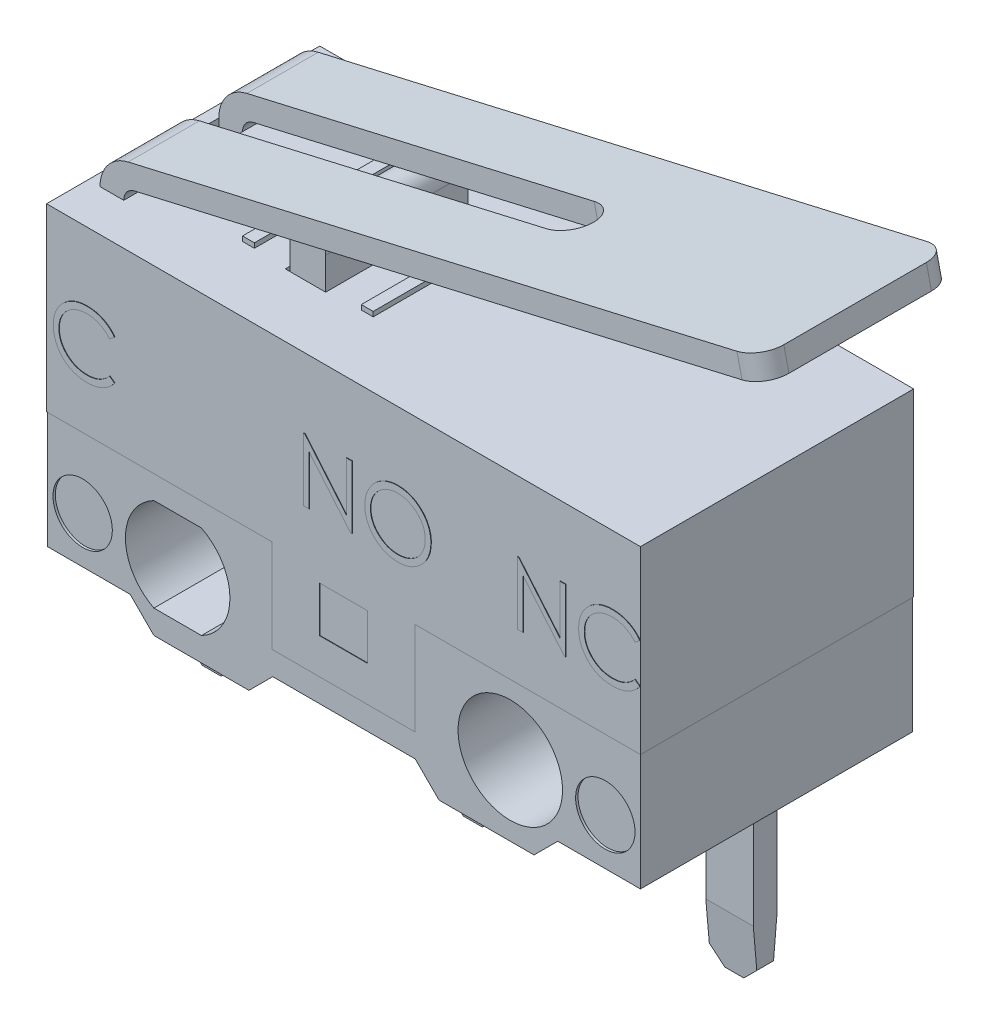
SolidWorks part; units mm, degrees
ref_plane "Plan de face" through (0, 0, 0) normal (0, 0, 1) x (1, 0, 0)
ref_plane "Plan de dessus" through (0, 0, 0) normal (0, 1, 0) x (1, 0, 0)
ref_plane "Plan de droite" through (0, 0, 0) normal (1, 0, 0) x (0, 0, -1)
sketch "Esquisse1" plane through (0, 0, 0) normal (0, 0, 1) x (1, 0, 0)
  line L1 (-6.5, 3.375) -> (6.5, 3.375)
  line L2 (-6.5, 3.375) -> (-6.5, -3.375)
  line L3 (-6.5, -3.375) -> (6.5, -3.375)
  line L4 (6.5, 3.375) -> (6.5, -3.375)
  line L5 (-6.5, 3.375) -> (6.5, -3.375) construction
  line L6 (-6.5, -3.375) -> (6.5, 3.375) construction
  point P0 (0, 0)
  dimension "D1" = 6.75
  dimension "D2" = 13
extrude "Boss.-Extru.1" add sketch "Esquisse1" along normal blind 5.75
ref_plane "Plan1" through (0, 0, 2.875) normal (0, 0, 1) x (1, 0, 0)
sketch "Esquisse6" plane through (0, 0, 5.75) normal (0, 0, 1) x (1, 0, 0)
  line L0 (-6.5, -2.875) -> (-4.5, -2.875)
  line L1 (-6.5, 3.375) -> (-6.5, -3.375) construction
  line L2 (-4.5, -2.875) -> (-4, -3.375)
  line L3 (-6.5, -3.375) -> (6.5, -3.375) construction
  line L4 (-4, -3.375) -> (-2, -3.375)
  line L5 (-2, -3.375) -> (-1.5, -2.875)
  line L6 (-1.5, -2.875) -> (1.5, -2.875)
  line L7 (1.5, -2.875) -> (2, -3.375)
  line L8 (2, -3.375) -> (4, -3.375)
  line L9 (4, -3.375) -> (4.5, -2.875)
  line L10 (4.5, -2.875) -> (6.5, -2.875)
  line L11 (6.5, -3.375) -> (6.5, 3.375) construction
  line L12 (6.5, -2.875) -> (6.5, -4.2145)
  line L13 (6.5, -4.2145) -> (-6.5, -4.2145)
  line L14 (-6.5, -4.2145) -> (-6.5, -2.875)
  dimension "D1" = 0.5
  dimension "D2" = 135
  dimension "D3" = 135
  dimension "D4" = 135
  dimension "D5" = 2
  dimension "D6" = 2
  dimension "D7" = 2
  dimension "D8" = 2
extrude "Enlèv. mat.-Extru.1" cut sketch "Esquisse6" against normal up to surface (5.75 mm away) up to face at (0, 0, 0)
sketch "Esquisse4" plane through (0, 0, 2.875) normal (0, 0, 1) x (1, 0, 0)
  line L0 (-6, -2.875) -> (-6, -6.125)
  line L9 (-5, -6.125) -> (-5, -2.875)
  line L10 (-5, -2.875) -> (-6, -2.875)
  line L11 (-5.5, -2.875) -> (-5.5, -7.9439) construction
  line L15 (-6, -6.125) -> (-5, -6.125)
  line L16 (-4.5, -2.875) -> (-6.5, -2.875) construction
  line L17 (-6.5, 3.375) -> (-6.5, -2.875) construction
  dimension "D1" = 1
  dimension "D2" = 1
  dimension "D4" = 3.25
extrude "Boss.-Extru.2" add sketch "Esquisse4" along normal blind 0.25 and the other way blind 0.25
chamfer "Chanfrein1" distance 0.3 angle 45 2 edges at (-5, -6.125, 2.875) (-6, -6.125, 2.875)
chamfer "Chanfrein2" distance 0.1 angle 85 2 edges at (-5.5, -6.125, 2.625) (-5.5, -6.125, 3.125)
pattern_linear "Répétition linéaire1" count 3 spacing 5.5 along (1, 0, 0) of "Boss.-Extru.2", "Chanfrein1", "Chanfrein2"
sketch "Esquisse7" plane through (0, 0, 5.75) normal (0, 0, 1) x (1, 0, 0)
  line L0 (-4, -2.875) -> (-3, -2.875)
  line L1 (-4, -0.9154) -> (-3, -0.9154)
  line L2 (-3.5, -1.8952) -> (3.5, -1.8952) construction
  line L3 (-4, -3.375) -> (-2, -3.375) construction
  line L4 (-6.5, 3.375) -> (-6.5, -2.875) construction
  line L5 (6.5, -2.875) -> (6.5, 3.375) construction
  arc A0 (-4, -0.9154) -> (-4, -2.875) centre (-3.5, -1.8952) ccw
  arc A1 (-3, -0.9154) -> (-3, -2.875) centre (-3.5, -1.8952) cw
  circle A2 centre (3.5, -1.8952) radius 1.1
  dimension "D1" = 1.1
  dimension "D3" = 1.1
  dimension "D4" = 2.2
  dimension "D2" = 1
  dimension "D5" = 0.5
  dimension "D6" = 3
  dimension "D7" = 3
extrude "Enlèv. mat.-Extru.2" cut sketch "Esquisse7" against normal up to surface (5.75 mm away) up to face at (0, -2, 0)
sketch "Esquisse8" plane through (0, 0, 5.75) normal (0, 0, 1) x (1, 0, 0)
  line L0 (-6.5, -0.4154) -> (-1.5, -0.4154)
  line L1 (-6.5, 3.375) -> (-6.5, -2.875) construction
  line L2 (-1.5, -0.4154) -> (-1.5, -2.375)
  line L3 (-1.5, -2.375) -> (1.5, -2.375)
  line L4 (1.5, -2.375) -> (1.5, -0.4154)
  line L5 (1.5, -0.4154) -> (6.5, -0.4154)
  line L6 (6.5, -2.875) -> (6.5, 3.375) construction
  line L7 (6.5, -0.4154) -> (6.5, -4.9919)
  line L8 (6.5, -4.9919) -> (-6.5, -4.9919)
  line L9 (-6.5, -4.9919) -> (-6.5, -0.4154)
  line L10 (1.5, -2.875) -> (-1.5, -2.875) construction
  line L11 (-3, -0.9154) -> (-4, -0.9154) construction
  line L13 (-0.5, -0.6654) -> (0.5, -0.6654)
  line L14 (-0.5, -0.6654) -> (-0.5, -1.625)
  line L15 (-0.5, -1.625) -> (0.5, -1.625)
  line L16 (0.5, -0.6654) -> (0.5, -1.625)
  line L17 (-0.5, -0.6654) -> (0.5, -1.625) construction
  line L18 (-0.5, -1.625) -> (0.5, -0.6654) construction
  point P21 (0, -1.1452)
  dimension "D1" = 0.5
  dimension "D2" = 0.5
  dimension "D3" = 0.25
  dimension "D4" = 1
  dimension "D5" = 1
  dimension "D6" = 0.75
extrude "Enlèv. mat.-Extru.3" cut sketch "Esquisse8" against normal blind 0.01
sketch "Esquisse9" plane through (0, 0, 5.74) normal (0, 0, 1) x (1, 0, 0)
  line L0 (-5.5, -1.8952) -> (5.5, -1.8952) construction
  line L1 (6.5, -2.875) -> (6.5, -0.4154) construction
  line L2 (-6.5, -0.4154) -> (-6.5, -2.875) construction
  circle A0 centre (-5.5, -1.8952) radius 0.625
  circle A1 centre (5.5, -1.8952) radius 0.625
  point P4 (3.5, -1.8952)
  dimension "D1" = 1.25
  dimension "D2" = 1.25
  dimension "D3" = 1
  dimension "D4" = 1
extrude "Enlèv. mat.-Extru.4" cut sketch "Esquisse9" against normal blind 0.05
mirror "Symétrie1" about plane through (0, 0, 2.875) normal (0, 0, 1) of "Enlèv. mat.-Extru.4", "Enlèv. mat.-Extru.3"
sketch "Esquisse10" plane through (-6.5, 0, 0) normal (-1, 0, 0) x (0, 0, 1)
  line L1 (0.01, -2.875) -> (5.74, -2.875)
  line L2 (0.01, -2.875) -> (0.01, -0.4154)
  line L3 (0.01, -0.4154) -> (5.74, -0.4154)
  line L4 (5.74, -2.875) -> (5.74, -0.4154)
extrude "Enlèv. mat.-Extru.5" cut sketch "Esquisse10" against normal blind 0.01
sketch "Esquisse11" plane through (6.5, 0, 0) normal (1, 0, 0) x (0, 0, -1)
  line L1 (-5.74, -2.875) -> (-0.01, -2.875)
  line L2 (-5.74, -2.875) -> (-5.74, -0.4154)
  line L3 (-5.74, -0.4154) -> (-0.01, -0.4154)
  line L4 (-0.01, -2.875) -> (-0.01, -0.4154)
extrude "Enlèv. mat.-Extru.6" cut sketch "Esquisse11" against normal blind 0.01
sketch "Esquisse12" plane through (0, 0, 5.75) normal (0, 0, 1) x (1, 0, 0)
  line L0 (-6.2, 0.5846) -> (-4.55, 0.5846) construction
  line L4 (-1, 0.5846) -> (2.5, 0.5846) construction
  line L5 (3.5, 0.5846) -> (6.2, 0.5846) construction
  line L6 (-1.5, -0.4154) -> (-6.5, -0.4154) construction
  line L7 (-6.5, 3.375) -> (-6.5, -0.4154) construction
  line L8 (6.5, -0.4154) -> (6.5, 3.375) construction
  text T0 "C" font "Century Gothic" height in points 5
  text T1 "NO" font "Century Gothic" height in points 5
  text T2 "NC" font "Century Gothic" height in points 5
  dimension "D1" = 1
  dimension "D2" = 1.65
  dimension "D3" = 0.3
  dimension "D4" = 0.3
  dimension "D5" = 2.7
  dimension "D6" = 3.5
  dimension "D7" = 1
extrude "Boss.-Extru.3" add sketch "Esquisse12" along normal blind 0.01
sketch "Esquisse13" plane through (0, 0, 2.875) normal (0, 0, 1) x (1, 0, 0)
  line L0 (-1.75, 4) -> (-1.75, 3.375)
  line L1 (6.5, 3.375) -> (-6.5, 3.375) construction
  line L2 (-1.75, 3.375) -> (-2.5, 3.375)
  line L3 (-2.5, 3.375) -> (-2.5, 4)
  line L4 (-4.7467, 4.375) -> (-2.1308, 4.375) construction
  line L5 (-6.5, 3.375) -> (-6.5, -0.4154) construction
  line L6 (-3.5, 3.375) -> (-3.5, 3.475)
  line L7 (-3.5, 3.475) -> (-3.25, 3.475)
  line L8 (-3.25, 3.475) -> (-3.25, 3.375)
  line L9 (-3.25, 3.375) -> (-3.5, 3.375)
  line L10 (-1, 3.375) -> (-1, 3.475)
  line L11 (-1, 3.475) -> (-0.75, 3.475)
  line L12 (-0.75, 3.475) -> (-0.75, 3.375)
  line L13 (-0.75, 3.375) -> (-1, 3.375)
  arc A0 (-2.5, 4) -> (-1.75, 4) centre (-2.125, 4) cw
  dimension "D1" = 0.75
  dimension "D2" = 1
  dimension "D3" = 4
  dimension "D4" = 0.1
  dimension "D5" = 0.75
  dimension "D6" = 0.75
  dimension "D7" = 0.25
  dimension "D8" = 0.25
extrude "Boss.-Extru.4" add sketch "Esquisse13" along normal blind 1.5 and the other way blind 1.5
sketch "Esquisse14" plane through (0, 3.375, 0) normal (0, 1, 0) x (1, 0, 0)
  line L1 (-2.5, -1.375) -> (-1.75, -1.375)
  line L2 (-2.5, -1.375) -> (-2.5, -4.375)
  line L3 (-2.5, -4.375) -> (-1.75, -4.375)
  line L4 (-1.75, -1.375) -> (-1.75, -4.375)
  line L8 (-6.5, -5.75) -> (-6.5, 0) construction
  line L9 (-6, -0.875) -> (-5.5, -0.875)
  line L10 (-6, -0.875) -> (-6, -4.875)
  line L11 (-6, -4.875) -> (-5.5, -4.875)
  line L12 (-2.55, -1.325) -> (-2.55, -4.425)
  line L13 (-2.55, -4.425) -> (-1.7, -4.425)
  line L14 (-1.7, -4.425) -> (-1.7, -1.325)
  line L15 (-1.7, -1.325) -> (-2.55, -1.325)
  line L16 (-2.55, -1.325) -> (-2.55, -4.425)
  line L17 (-2.55, -4.425) -> (-1.7, -4.425)
  line L18 (-1.7, -4.425) -> (-1.7, -1.325)
  line L19 (-1.7, -1.325) -> (-2.55, -1.325)
  line L20 (-5.5, -0.875) -> (-5.5, -4.875)
  line L21 (-6, -2.875) -> (-3.9155, -2.875) construction
  line L22 (-3.7125, -2.875) -> (3.7125, -2.875) construction
  dimension "D2" = 0.5
  dimension "D3" = 0.5
  dimension "D4" = 4
  dimension "D1" = 0.05
extrude "Enlèv. mat.-Extru.7" cut sketch "Esquisse14" against normal blind 2
sketch "Esquisse16" plane through (0, 0, 0.875) normal (0, 0, 1) x (1, 0, 0)
  line L0 (-6, 2.375) -> (-5.5, 2.375)
  line L1 (-5.5, 2.375) -> (-5.5, 3.375)
  line L2 (-5.2748, 3.6581) -> (8, 6.7211)
  line L3 (8, 6.7211) -> (7.8921, 7.1888)
  line L4 (7.8921, 7.1888) -> (-5.4072, 4.1201)
  line L5 (-6, 3.375) -> (-6, 2.375)
  line L6 (-6.5, 3.375) -> (-6.5, -0.4154) construction
  line L7 (6.5, 3.375) -> (-6.5, 3.375) construction
  line L8 (8, 6.7211) -> (8, 3.9001) construction
  line L9 (6.5, -0.4154) -> (6.5, 3.375) construction
  line L10 (6.5, 2.5145) -> (6.5, 9.8405) construction
  arc A0 (-5.5, 3.375) -> (-5.2748, 3.6581) centre (-5.2095, 3.375) cw
  arc A2 (-1.75, 4) -> (-2.5, 4) centre (-2.125, 4) ccw construction
  arc A3 (-6, 3.375) -> (-5.4072, 4.1201) centre (-5.2353, 3.375) cw
  point P8 (6.5, 6.375)
  dimension "D1" = 0.5
  dimension "D2" = 0.5
  dimension "D3" = 0.48
  dimension "D4" = 1
  dimension "D5" = 1.5
  dimension "D6" = 3
extrude "Boss.-Extru.13" add sketch "Esquisse16" along normal blind 4 separate body contours A3 L4 L3 L2 A0 L1 L0 L5
sketch "Esquisse17" plane through (0, 0, 2.875) normal (0, 0, 1) x (1, 0, 0)
  line L6 (-5.4072, 4.1201) -> (2.3879, 5.9188)
  line L7 (7.8921, 7.1888) -> (-5.4072, 4.1201) construction
  line L8 (2.3879, 5.9188) -> (2.4959, 5.4511)
  line L9 (-5.2748, 3.6581) -> (8, 6.7211) construction
  line L10 (2.4959, 5.4511) -> (-5.2748, 3.6581)
  line L12 (-6, 3.375) -> (-6, 2.375)
  line L13 (-6, 2.375) -> (-5.5, 2.375)
  line L14 (-5.5, 2.375) -> (-5.5, 3.375)
  line L15 (-5.2748, 3.6581) -> (8, 6.7211)
  line L16 (8, 6.7211) -> (7.8921, 7.1888)
  line L17 (7.8921, 7.1888) -> (-5.4072, 4.1201)
  line L18 (-6, 3.375) -> (-6, 2.375)
  line L19 (-6, 2.375) -> (-5.5, 2.375)
  line L20 (-5.5, 2.375) -> (-5.5, 3.375)
  arc A4 (-5.4072, 4.1201) -> (-6, 3.375) centre (-5.2353, 3.375) ccw
  arc A5 (-5.2748, 3.6581) -> (-5.5, 3.375) centre (-5.2095, 3.375) ccw
  arc A6 (-5.4072, 4.1201) -> (-6, 3.375) centre (-5.2353, 3.375) ccw
  arc A7 (-5.2748, 3.6581) -> (-5.5, 3.375) centre (-5.2095, 3.375) ccw
  dimension "D2" = 8
  dimension "D1" = 0
extrude "Enlèv. mat.-Extru.8" cut sketch "Esquisse17" against normal blind 0.5 and the other way blind 0.5
fillet "Congé1" radius 0.5 2 edges at (2.4419, 5.6849, 3.375) (2.4419, 5.6849, 2.375)
fillet "Congé3" radius 0.5 2 edges at (7.946, 6.955, 0.875) (7.946, 6.955, 4.875)
sketch "Esquisse19" plane through (0, 0, 0) normal (0, 0, -1) x (-1, 0, 0)
  line L0 (-4.5, -0.1654) -> (5.7239, -0.1654) construction
  line L1 (-6.5, -0.4154) -> (-1.5, -0.4154) construction
  line L2 (-6.5, -0.4154) -> (-6.5, 3.375) construction
  text T0 "2A125VAC" font "Century Gothic" height in points 4
  dimension "D1" = 0.25
  dimension "D2" = 2
extrude "Boss.-Extru.14" add sketch "Esquisse19" along normal blind 0.05
other "Move Face1" face at (-6.49, -1.6452, 2.875) face at (-6.5, 1.4798, 2.875) parameters "D1"=0.25
other "Move Face2" face at (6.49, -1.6452, 2.875) face at (6.5, 1.4798, 2.875) parameters "D1"=0.25
